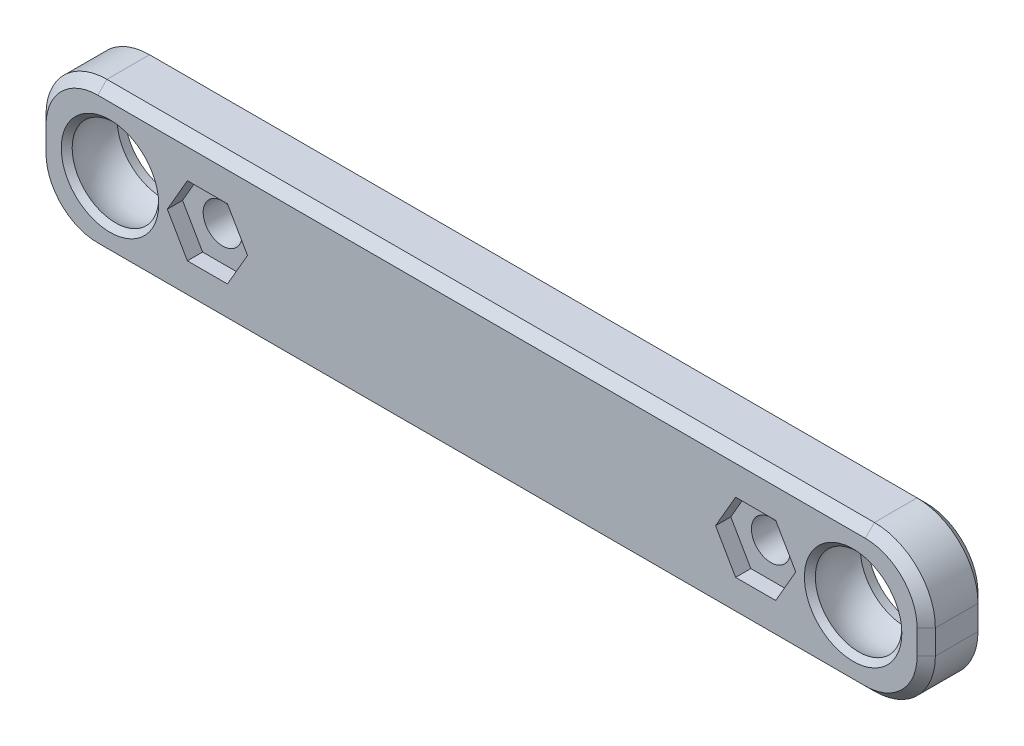
SolidWorks part; units mm, degrees
material "ABS"
ref_plane "Front Plane" through (0, 0, 0) normal (0, 0, 1) x (1, 0, 0)
ref_plane "Top Plane" through (0, 0, 0) normal (0, 1, 0) x (1, 0, 0)
ref_plane "Right Plane" through (0, 0, 0) normal (1, 0, 0) x (0, 0, -1)
sketch "Sketch1" plane through (0, 0, 0) normal (0, 0, 1) x (1, 0, 0)
  line L1 (-36.5, 6) -> (36.5, 6)
  line L2 (-36.5, 6) -> (-36.5, -6)
  line L3 (-36.5, -6) -> (36.5, -6)
  line L4 (36.5, 6) -> (36.5, -6)
  line L5 (-36.5, 6) -> (36.5, -6) construction
  line L6 (-36.5, -6) -> (36.5, 6) construction
  circle A0 centre (-30.5, 0) radius 2.5
  circle A1 centre (30.5, 0) radius 2.5
  point P0 (0, 0)
  dimension "D3" = 5
  dimension "D6" = 5
  dimension "D1" = 61
  dimension "D2" = 6
  dimension "D4" = 30.5
  dimension "D5" = 12
extrude "Boss-Extrude1" add sketch "Sketch1" along normal mid plane 5
sketch "Sketch2" plane through (0, 0, 0) normal (0, 1, 0) x (1, 0, 0)
  line L0 (-30.5, -14.7503) -> (-30.5, 7.6157) construction
  line L1 (-36.5, -2.5) -> (-36.5, 2.5) construction
  line L2 (-30.5, -4.1) -> (-30.5, 4.1)
  circle A0 centre (-30.5, 0) radius 4.1
  point P7 (-36.5, 0)
  dimension "D2" = 8.2
  dimension "D1" = 6
revolve "Cut-Revolve1" cut sketch "Sketch2" angle 360 about L0 region at (-28.7599, 0, 0)
mirror "Mirror1" about plane through (0, 0, 0) normal (1, 0, 0) of "Cut-Revolve1"
fillet "Fillet1" radius 5 4 edges at (36.5, 6, 0) (36.5, -6, 0) (-36.5, 6, 0) (-36.5, -6, 0)
chamfer "Chamfer1" distance 0.75 angle 45 20 edges at (-35.0355, 4.5355, -2.5) (-36.5, 0, -2.5) (-35.0355, -4.5355, -2.5) (0, -6, -2.5) (35.0355, -4.5355, -2.5) (36.5, 0, -2.5) (35.0355, 4.5355, -2.5) (0, 6, -2.5) (-27.2504, 0, -2.5) (33.7496, 0, -2.5) (35.0355, -4.5355, 2.5) (0, -6, 2.5) (-35.0355, -4.5355, 2.5) (-36.5, 0, 2.5) (-35.0355, 4.5355, 2.5) (0, 6, 2.5) (35.0355, 4.5355, 2.5) (36.5, 0, 2.5) (-27.2504, 0, 2.5) (33.7496, 0, 2.5) first distance on face at (33.7496, 0, -2.5) first distance on face at (-27.2504, 0, 2.5) first distance on face at (33.7496, 0, 2.5) first distance on face at (34.5178, -4.0178, 0) first distance on face at (0, -6, 0) first distance on face at (-34.5178, -4.0178, 0) first distance on face at (-36.5, 0, 0) first distance on face at (-34.5178, 4.0178, 0) first distance on face at (0, 6, 0) first distance on face at (34.5178, 4.0178, 0) first distance on face at (36.5, 0, 0)
sketch "Sketch3" plane through (0, 0, 0) normal (0, 0, 1) x (1, 0, 0)
  point P0 (-30.5, 0)
  point P1 (30.5, 0)
hole_wizard "CSK for M3 Countersunk Flat Head Screw1" positions "Sketch4" profile "Sketch5" countersink size "M3" standard "ISO" end condition through all
sketch "Sketch4" plane through (0, 0, -2.5) normal (0, 0, -1) x (-1, 0, 0)
  point P0 (-22.5, 0)
  point P2 (22.5, 0)
  dimension "D1" = 8
  dimension "D2" = 8
sketch "Sketch5" plane through (22.5, 0, -2.5) normal (1, 0, 0) x (0, 1, 0)
  line L0 (0, 0) -> (0, 5)
  line L1 (0, 5) -> (1.6, 5)
  line L2 (1.6, 5) -> (1.6, 1.55)
  line L3 (1.6, 1.55) -> (3.15, 0)
  line L5 (3.15, 0) -> (0, 0)
  line L6 (-1.6, 1.55) -> (-3.15, 0) construction
  line L11 (0, -6.35) -> (0, 107.95) construction
  dimension "Thru Hole Dia." = 3.2
  dimension "Thru Hole Depth" = 5
  dimension "Near C'Sink Dia." = 6.3
  dimension "Near C'Sink Angle" = 90
sketch "Sketch6" plane through (0, 0, 2.5) normal (0, 0, 1) x (1, 0, 0)
  line L1 (-19.2091, 0) -> (-20.8546, 2.85)
  line L2 (-20.8546, 2.85) -> (-24.1454, 2.85)
  line L3 (-24.1454, 2.85) -> (-25.7909, 0)
  line L4 (-25.7909, 0) -> (-24.1454, -2.85)
  line L5 (-24.1454, -2.85) -> (-20.8546, -2.85)
  line L6 (-20.8546, -2.85) -> (-19.2091, 0)
  line L7 (19.2091, 0) -> (20.8546, -2.85)
  line L8 (20.8546, -2.85) -> (24.1454, -2.85)
  line L9 (24.1454, -2.85) -> (25.7909, 0)
  line L10 (25.7909, 0) -> (24.1454, 2.85)
  line L11 (24.1454, 2.85) -> (20.8546, 2.85)
  line L12 (20.8546, 2.85) -> (19.2091, 0)
  circle A0 centre (-22.5, 0) radius 2.85 construction
  circle A1 centre (22.5, 0) radius 2.85 construction
  dimension "D1" = 5.7
  dimension "D2" = 5.7
extrude "Cut-Extrude1" cut sketch "Sketch6" against normal blind 1.25
equation "\"D4@Sketch1\"=\"D1@Sketch1\"/2"
equation "\"D6@Sketch1\"=\"D3@Sketch1\""
